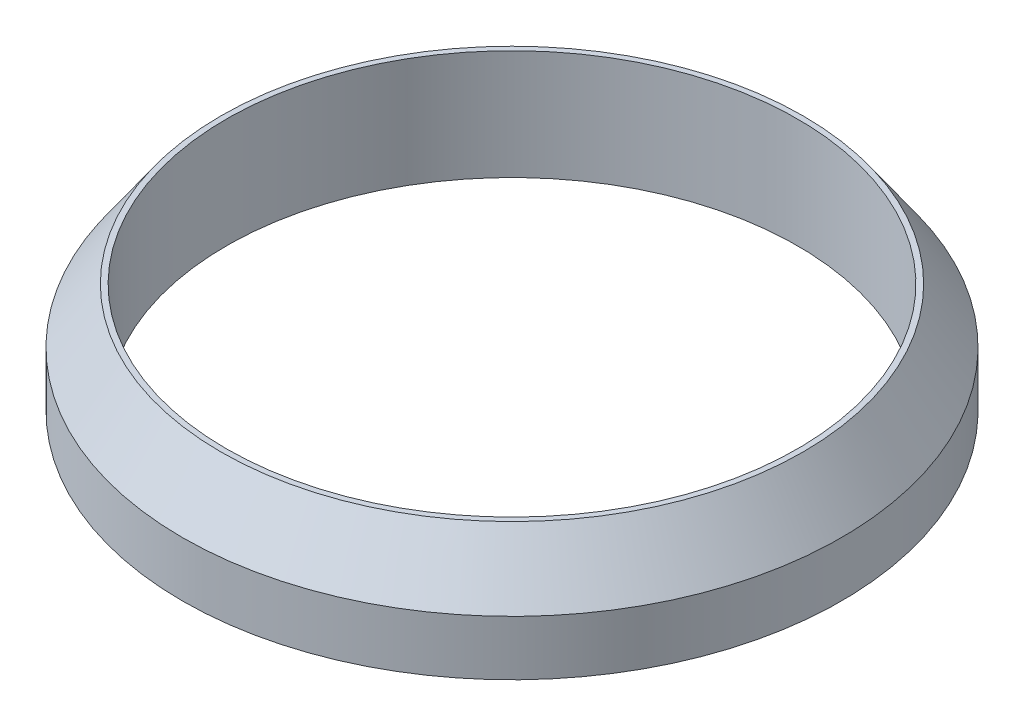
SolidWorks part; units mm, degrees
ref_plane "Front Plane" through (0, 0, 0) normal (0, 0, 1) x (1, 0, 0)
ref_plane "Top Plane" through (0, 0, 0) normal (0, 1, 0) x (1, 0, 0)
ref_plane "Right Plane" through (0, 0, 0) normal (1, 0, 0) x (0, 0, -1)
sketch "Sketch2" plane through (0, 0, 0) normal (0, 1, 0) x (1, 0, 0)
  circle A0 centre (0, 0) radius 76.2
  circle A1 centre (0, 0) radius 66.04
  dimension "D1" = 152.4
  dimension "D2" = 132.08
extrude "Boss-Extrude1" add sketch "Sketch2" along normal blind 25.4
sketch "Sketch5" plane through (0, 0, 0) normal (1, 0, 0) x (0, 0, -1)
  line L4 (0, 0) -> (0, 50000) construction
  line L5 (-76.2, 12.7) -> (-67.31, 25.4)
  line L6 (-76.2, 25.4) -> (-76.2, 0) construction
  line L7 (76.2, 25.4) -> (-76.2, 25.4) construction
  line L8 (-67.31, 25.4) -> (-76.2, 25.4)
  line L9 (-76.2, 25.4) -> (-76.2, 12.7)
  point P11 (-69.3676, 25.4)
  dimension "D1" = 67.31
revolve "Cut-Revolve2" cut sketch "Sketch5" angle 360 about L4
